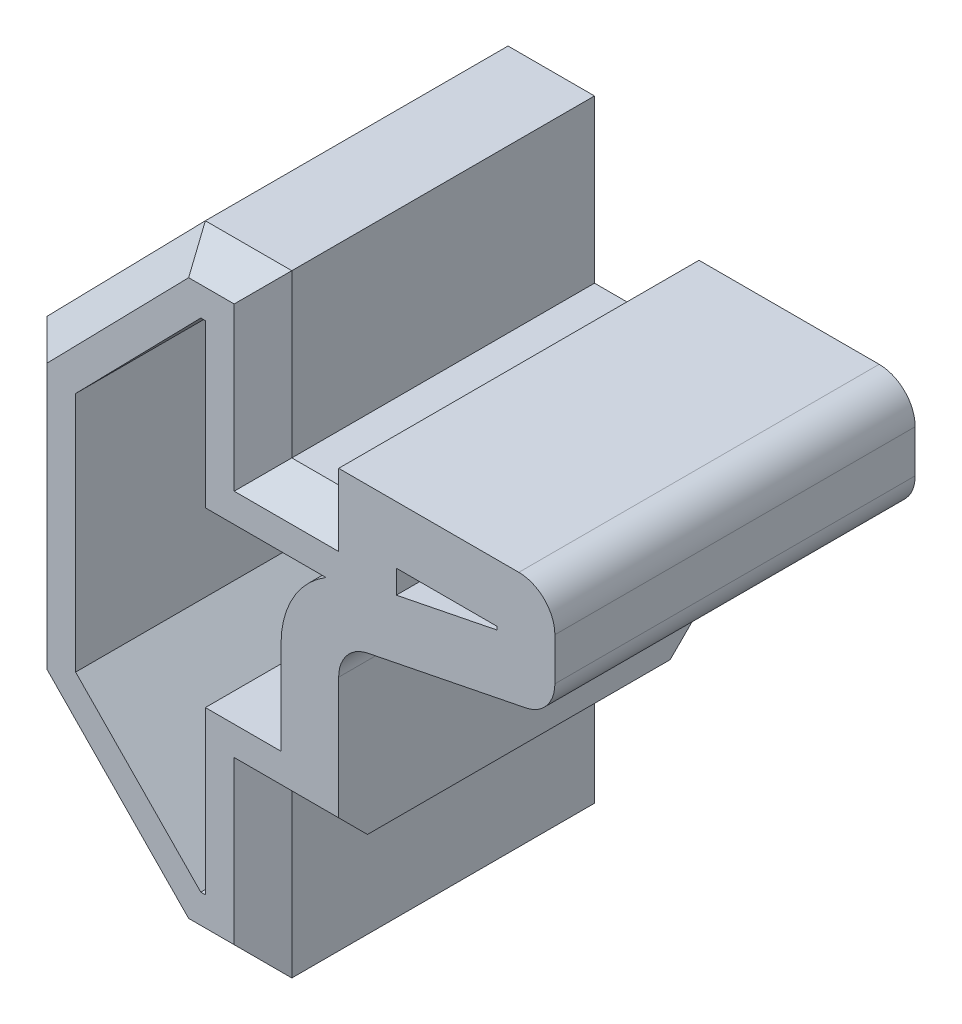
SolidWorks part; units mm, degrees
ref_plane "Alzado" through (0, 0, 0) normal (0, 0, 1) x (1, 0, 0)
ref_plane "Planta" through (0, 0, 0) normal (0, 1, 0) x (1, 0, 0)
ref_plane "Vista lateral" through (0, 0, 0) normal (1, 0, 0) x (0, 0, -1)
sketch "Croquis1" plane through (0, 0, 0) normal (0, 0, 1) x (1, 0, 0)
  line L0 (0, 0) -> (0, 5301.9663) construction
  line L1 (0, 0) -> (5301.9663, 0) construction
  line L2 (-4.8553, 4) -> (5297.111, 4) construction
  line L3 (0, 4) -> (-2.1, 4)
  line L4 (-8.9, 5.9678) -> (-8.9, -5295.9985) construction
  line L5 (-2.1, 7.8714) -> (-2.1, -5294.095) construction
  line L6 (-2.1, 4) -> (-2.1, 8.5)
  line L8 (-8.9, 4) -> (-8.9, -4)
  line L10 (-2.1, -4) -> (-2.1, -8.5)
  line L11 (0, -4) -> (-2.1, -4)
  line L12 (0, 4) -> (0, -4)
  line L13 (-4.5, -15.5102) -> (-4.5, 49984.4898) construction
  line L14 (-2.1, -8.5) -> (-4.5, -8.5)
  line L15 (-4.5, -8.5) -> (-8.9, -4)
  line L16 (-4.5, 8.5) -> (-8.9, 4)
  line L17 (-2.1, 8.5) -> (-4.5, 8.5)
  point P17 (-8.9, 0)
  dimension "D1" = 8
  dimension "D2" = 6.8
  dimension "D3" = 2.1
  dimension "D4" = 8
  dimension "D5" = 17
  dimension "D6" = 2.4
extrude "Saliente-Extruir1" add sketch "Croquis1" along normal mid plane 10
sketch "Croquis2" plane through (0, 0, -5) normal (0, 0, -1) x (-1, 0, 0)
  line L0 (-13.3591, 5.2) -> (49986.6409, 5.2) construction
  line L1 (0, 4) -> (2.1, 4) construction
  line L2 (0, 4) -> (0, 5.2)
  line L3 (0, 5.2) -> (-6, 5.2)
  line L4 (-6, 5.2) -> (-6, 2.2)
  line L5 (-6, 2.2) -> (0, 1)
  line L6 (0, -4) -> (0, 4) construction
  line L7 (0, 1) -> (0, 4)
  dimension "D1" = 1.2
  dimension "D2" = 3
  dimension "D3" = 3
  dimension "D4" = 6
extrude "Saliente-Extruir2" add sketch "Croquis2" against normal through all
fillet "Redondeo1" radius 1 3 edges at (0, 1, 0) (6, 2.2, 0) (6, 5.2, 0)
shell "Vaciado1" thickness 1.6 removed face at (-0.7055, 1.2475, 5) removed face at (-0.7055, 1.2475, -5)
chamfer "Chaflán1" distance 0.8 angle 45 18 edges at (-2.1, -6.25, 5) (-2.1, 6.25, 5) (-8.9, 0, 5) (-1.05, -4, 5) (-1.05, 4, 5) (-1.05, -4, -5) (-1.05, 4, -5) (-2.1, 6.25, -5) (-2.1, -6.25, -5) (-8.9, 0, -5) (-3.3, -8.5, -5) (-6.7, -6.25, -5) (-3.3, 8.5, -5) (-6.7, 6.25, -5) (-3.3, -8.5, 5) (-6.7, -6.25, 5) (-6.7, 6.25, 5) (-3.3, 8.5, 5)
